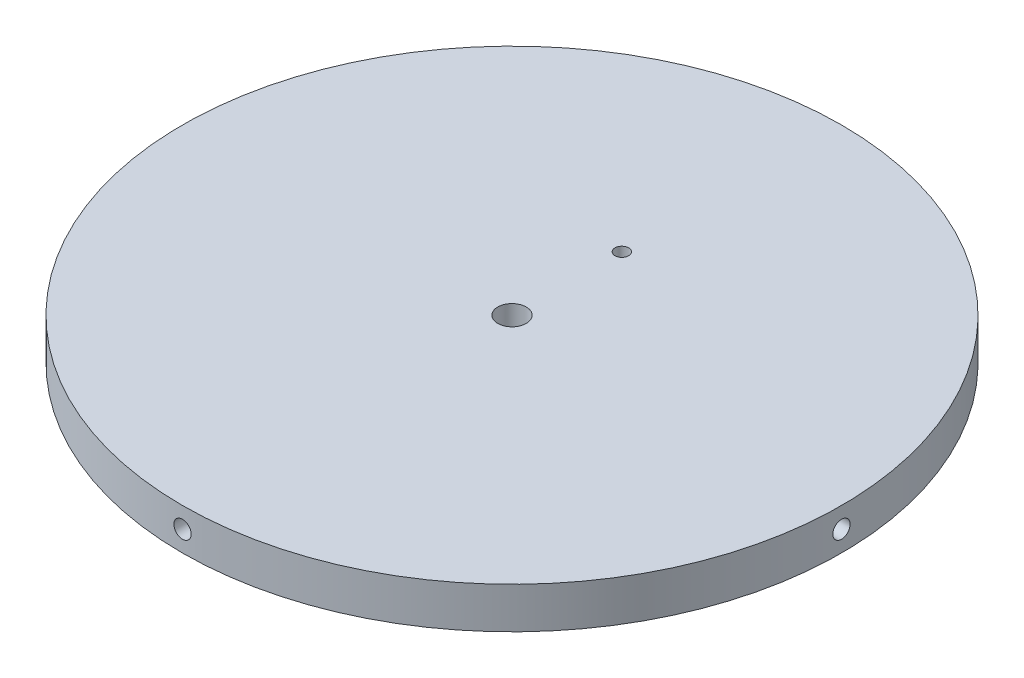
SolidWorks part; units mm, degrees
material "6061-T6 (SS)"
ref_plane "Front Plane" through (0, 0, 0) normal (0, 0, 1) x (1, 0, 0)
ref_plane "Top Plane" through (0, 0, 0) normal (0, 1, 0) x (1, 0, 0)
ref_plane "Right Plane" through (0, 0, 0) normal (1, 0, 0) x (0, 0, -1)
sketch "Sketch1" plane through (0, 0, 0) normal (0, 1, 0) x (1, 0, 0)
  circle A0 centre (0, 0) radius 76.2
  circle A1 centre (0, 0) radius 3.3
  circle A2 centre (0, 25.4) radius 1.5875
  point P6 (0, 0)
  dimension "D1" = 152.4
  dimension "D2" = 6.6
  dimension "D3" = 3.175
  dimension "D4" = 25.4
extrude "Boss-Extrude1" add sketch "Sketch1" along normal mid plane 9.525
ref_plane "Plane1" through (0, 0, 76.2) normal (0, 0, 1) x (1, 0, 0)
sketch "Sketch5" plane through (0, 0, 76.2) normal (0, 0, 1) x (1, 0, 0)
  circle A0 centre (0, 0) radius 2
  dimension "D1" = 4
extrude "Cut-Extrude1" cut sketch "Sketch5" against normal blind 19.05
sketch "Sketch14" plane through (0, 0, 0) normal (0, 0, 1) x (1, 0, 0)
  line L0 (0, -5.2723) -> (0, 5.2496)
pattern_circular "CirPattern5" count 4 over 360 about axis through (0, -5.2723, 0) along (0, 1, 0) of "Cut-Extrude1" reverse direction yes
